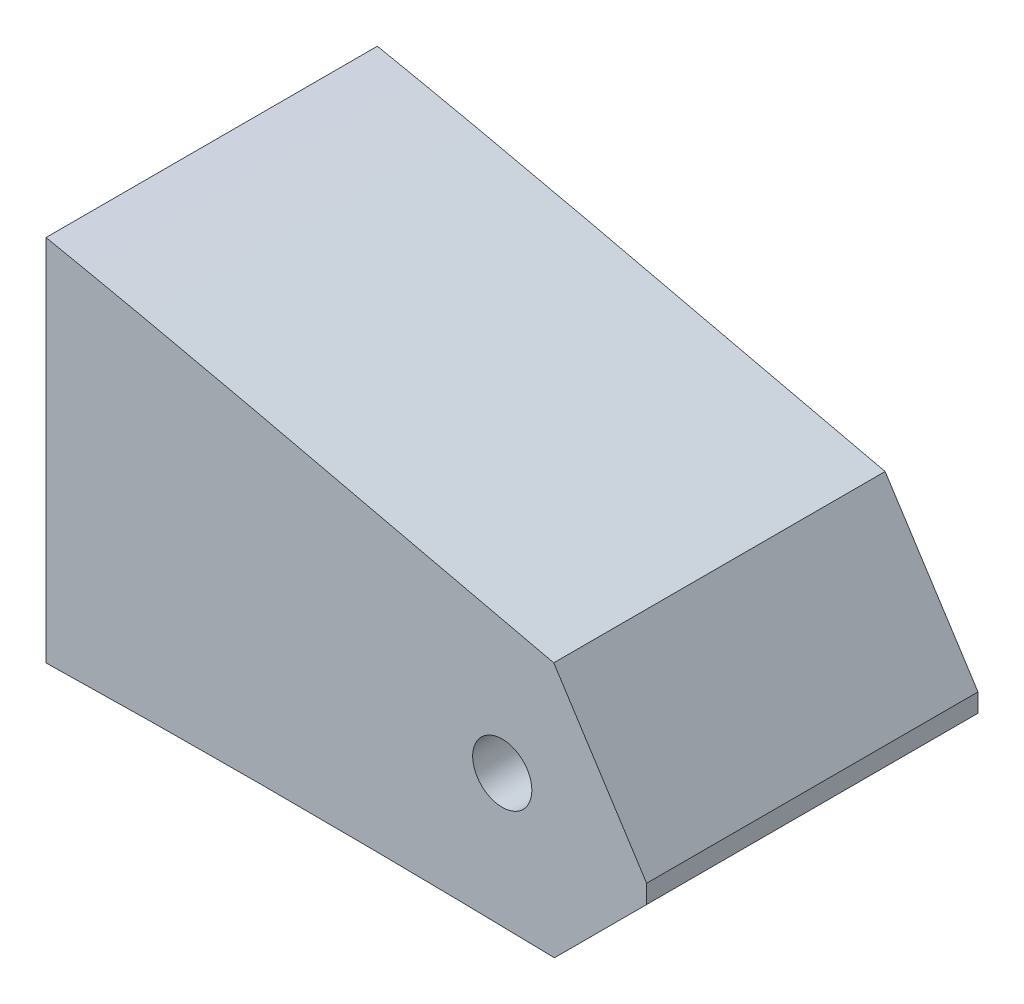
SolidWorks part; units mm, degrees
ref_plane "Front Plane" through (0, 0, 0) normal (0, 0, 1) x (1, 0, 0)
ref_plane "Top Plane" through (0, 0, 0) normal (0, 1, 0) x (1, 0, 0)
ref_plane "Right Plane" through (0, 0, 0) normal (1, 0, 0) x (0, 0, -1)
sketch "Sketch1" plane through (0, 0, 0) normal (0, 0, 1) x (1, 0, 0)
  line L1 (82.0002, -8.1862) -> (88.1854, -2.001)
  line L2 (88.1854, -2.001) -> (88.1854, -0.7622)
  line L3 (88.1854, -0.7622) -> (81.9567, 8.9274)
  circle A2 centre (78.503, 0.7896) radius 1.9844
  spline S0 degree 3 poles (-76.2636, -14.6303) (-75.3372, -19.8445) (-64.7299, -19.291) (-48.8118, -19.2228) (-26.1832, -15.0728) (18.2185, -8.2376) (55.3408, -7.5605) (82.0002, -8.1862) knots 0.037176 0.037176 0.037176 0.037176 0.117656 0.187766 0.340509 0.519846 1 1 1 1
  spline S1 degree 3 poles (81.9567, 8.9274) (63.0307, 13.2209) (32.9125, 21.0548) (-8.7883, 22.4934) (-37.0227, 17.0488) (-56.4688, 7.9424) (-69.7509, -1.1836) (-75.6535, -9.0885) (-76.2636, -14.6303) knots 0 0 0 0 0.32619 0.519062 0.695897 0.802481 0.877632 0.964219 0.964219 0.964219 0.964219
  dimension "D1" = 3.9688
  dimension "D2" = 158.2638
extrude "Boss-Extrude1" add sketch "Sketch1" along normal blind 22.225
sketch "Sketch2" plane through (0, 0, 22.225) normal (0, 0, 1) x (1, 0, 0)
  line L1 (-90.3718, 30.6925) -> (47.9035, 30.6925)
  line L2 (-90.3718, 30.6925) -> (-90.3718, -22.6703)
  line L3 (-90.3718, -22.6703) -> (47.9035, -22.6703)
  line L4 (47.9035, 30.6925) -> (47.9035, -22.6703)
  line L5 (88.1854, -2.001) -> (88.1854, -0.7622) construction
  dimension "D1" = 40.2819
extrude "Cut-Extrude1" cut sketch "Sketch2" against normal blind 28.956
